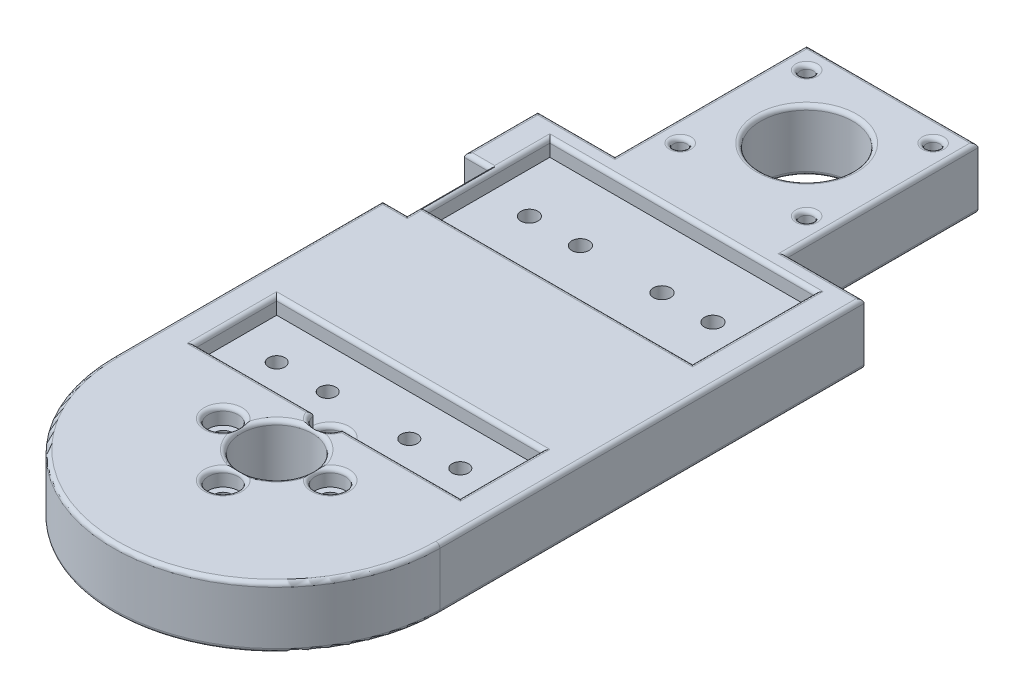
SolidWorks part; units mm, degrees
ref_plane "Ebene vorne" through (0, 0, 0) normal (0, 0, 1) x (1, 0, 0)
ref_plane "Ebene oben" through (0, 0, 0) normal (0, 1, 0) x (1, 0, 0)
ref_plane "Ebene rechts" through (0, 0, 0) normal (1, 0, 0) x (0, 0, -1)
sketch "Skizze1" plane through (0, 0, 0) normal (0, 1, 0) x (1, 0, 0)
  line L0 (-25.9794, -40) -> (25.9794, -40) construction
  line L2 (-40, 0) -> (-40, 104)
  line L4 (40, 0) -> (40, 104)
  line L5 (-40, 0) -> (40, 104) construction
  line L6 (-40, 104) -> (40, 0) construction
  line L9 (-40, 104) -> (-40, 78)
  line L12 (-40, 104) -> (40, 104)
  line L13 (-21.0848, 151) -> (20.9152, 109) construction
  line L21 (-21.0848, 104) -> (20.9152, 104)
  line L22 (-21.0848, 104) -> (-21.0848, 151)
  line L23 (-21.0848, 151) -> (20.9152, 151)
  line L24 (20.9152, 104) -> (20.9152, 151)
  line L25 (20.9152, 151) -> (-21.0848, 109) construction
  line L26 (0, 17.5) -> (0, 8.75) construction
  circle A0 centre (0, 0) radius 40
  circle A2 centre (-0.0848, 130) radius 11.3
  circle A3 centre (-15.5848, 145.5) radius 1.65
  circle A4 centre (15.4152, 145.5) radius 1.65
  circle A5 centre (15.4152, 114.5) radius 1.65
  circle A6 centre (-15.5848, 114.5) radius 1.65
  circle A7 centre (0, 0) radius 8.75
  circle A8 centre (0, 0) radius 17.5
  circle A17 centre (0, 13.125) radius 2.1
  circle A18 centre (13.125, 0) radius 2.1
  circle A19 centre (0, -13.125) radius 2.1
  circle A20 centre (-13.125, 0) radius 2.1
  point P7 (0, 52)
  point P11 (0, -40)
  point P31 (-0.0848, 130)
  point P35 (0, 0)
  point P36 (0, 13.125)
  point P44 (0, 0)
  point P52 (0, 0)
  dimension "D1" = 80
  dimension "D5" = 144
  dimension "D4" = 42
  dimension "D6" = 4
  dimension "D7" = 35
  dimension "D8" = 4
  dimension "D9" = 3.3
  dimension "D11" = 17.5
  dimension "D2" = 42
  dimension "D3" = 5
extrude "Aufsatz-Linear austragen1" add sketch "Skizze1" along normal blind 15 contours L12 L24 L23 L22 A6 A5 A4 A3 A2 | A0 L4 L12 L2 | A0 A8 | A8 A20 A19 A18 A17 A7
sketch "Skizze5" plane through (0, 15, 0) normal (0, 1, 0) x (1, 0, 0)
  line L0 (40, 0) -> (40, 104) construction
  line L1 (-25, 69.5) -> (40, 69.5)
  line L2 (-25, 69.5) -> (-25, 32.5)
  line L3 (-25, 32.5) -> (40, 32.5)
  line L4 (40, 69.5) -> (40, 32.5)
  line L5 (-25, 69.5) -> (40, 32.5) construction
  line L6 (-25, 32.5) -> (40, 69.5) construction
  line L7 (0, 0) -> (0, 22.5) construction
  line L8 (-25, 32.5) -> (40, 32.5)
  line L13 (20.9152, 104) -> (40, 104) construction
  line L14 (-32.5, 12.5) -> (32.5, 12.5)
  line L15 (-32.5, 12.5) -> (-32.5, 32.5)
  line L16 (-32.5, 32.5) -> (32.5, 32.5)
  line L17 (32.5, 12.5) -> (32.5, 32.5)
  line L18 (-32.5, 12.5) -> (32.5, 32.5) construction
  line L19 (-32.5, 32.5) -> (32.5, 12.5) construction
  point P4 (7.5, 51)
  point P13 (0, 22.5)
  dimension "D1" = 20
  dimension "D2" = 37
  dimension "D3" = 65
  dimension "D4" = 34.5
extrude "Schnitt-Linear austragen3" cut sketch "Skizze5" against normal blind 4 contours L14 L17 L3 L16 L15 region at (0, 15, -22.5)
sketch "Skizze6" plane through (0, 11, 0) normal (0, 1, 0) x (1, 0, 0)
  line L0 (-32.5, 22.5) -> (32.5, 22.5) construction
  line L1 (32.5, 12.5) -> (32.5, 32.5) construction
  line L3 (0, 22.5) -> (0, 3.2798) construction
  line L5 (32.5, 12.5) -> (32.5, 32.5) construction
  circle A0 centre (10, 22.5) radius 2
  circle A1 centre (-10, 22.5) radius 2
  circle A2 centre (22.5, 22.5) radius 2
  circle A3 centre (-22.5, 22.5) radius 2
  dimension "D2" = 4
  dimension "D3" = 4
  dimension "D1" = 10
  dimension "D4" = 12.5
extrude "Schnitt-Linear austragen4" cut sketch "Skizze6" against normal blind 11
sketch "Skizze14" plane through (0, 15, 0) normal (0, 1, 0) x (1, 0, 0)
  line L0 (-40, 104) -> (-40, 86) construction
  line L1 (-40, 0) -> (-40, 104) construction
  line L2 (-40, 104) -> (-21.0848, 104) construction
  line L4 (-40, 86) -> (-34, 86)
  line L5 (-40, 86) -> (-40, 66)
  line L6 (-40, 66) -> (-34, 66)
  line L7 (-34, 86) -> (-34, 66)
  line L8 (-40, 86) -> (-34, 66) construction
  line L9 (-40, 66) -> (-34, 86) construction
  point P9 (-37, 76)
  dimension "D1" = 20
  dimension "D2" = 18
  dimension "D3" = 6
extrude "Schnitt-Linear austragen11" cut sketch "Skizze14" against normal blind 15 contours L5 L4 L7 L6
sketch "Skizze15" plane through (-34, 0, 0) normal (-1, 0, 0) x (0, 0, 1)
  line L0 (-86, 0) -> (-86, 15) construction
  line L1 (-66, 0) -> (-66, 15) construction
  circle A1 centre (-80.5, 7.5) radius 2.25
  circle A2 centre (-71, 7.5) radius 2.25
  dimension "D1" = 4.5
  dimension "D2" = 4.5
  dimension "D3" = 9.5
  dimension "D4" = 5.5
  dimension "D5" = 5
extrude "Schnitt-Linear austragen12" cut sketch "Skizze15" against normal blind 6
sketch "Skizze19" plane through (0, 15, 0) normal (0, 1, 0) x (1, 0, 0)
  line L0 (0, 0) -> (-0.0848, 130) construction
  line L2 (-32.5551, 69.5) -> (32.4449, 69.5)
  line L3 (-32.5551, 69.5) -> (-32.5551, 99.5)
  line L4 (-32.5551, 99.5) -> (32.4449, 99.5)
  line L5 (32.4449, 69.5) -> (32.4449, 99.5)
  line L6 (-32.5551, 69.5) -> (32.4449, 99.5) construction
  line L7 (-32.5551, 99.5) -> (32.4449, 69.5) construction
  line L8 (20.9152, 104) -> (40, 104) construction
  point P4 (-0.0551, 84.5)
  dimension "D1" = 65
  dimension "D2" = 30
  dimension "D3" = 4.5
extrude "Schnitt-Linear austragen15" cut sketch "Skizze19" against normal blind 4
sketch "Skizze21" plane through (0, 11, 0) normal (0, 1, 0) x (1, 0, 0)
  line L1 (-0.0548, 84) -> (-0.0548, 95.2298) construction
  line L4 (32.4449, 69.5) -> (32.4449, 99.5) construction
  line L5 (-32.5551, 84.5) -> (32.4449, 84.5) construction
  line L6 (-32.5551, 99.5) -> (-32.5551, 69.5) construction
  circle A0 centre (22.4449, 84.5) radius 2.1
  circle A1 centre (9.9449, 84.5) radius 2.1
  circle A2 centre (-22.5545, 84.5) radius 2.1
  circle A3 centre (-10.0545, 84.5) radius 2.1
  point P13 (0, 0)
  point P18 (0, 0)
  point P19 (0, 0)
  dimension "D1" = 10
  dimension "D2" = 12.5
extrude "Schnitt-Linear austragen16" cut sketch "Skizze21" against normal blind 11
sketch "Skizze22" plane through (0, 0, 0) normal (0, -1, 0) x (1, 0, 0)
  line L0 (0, -84) -> (0, -79.7713) construction
  circle A0 centre (-22.5545, -84.5) radius 3.65
  circle A1 centre (-10.0545, -84.5) radius 3.65
  circle A2 centre (10.0545, -84.5) radius 3.65
  circle A3 centre (22.5545, -84.5) radius 3.65
  circle A4 centre (-22.5545, -84.5) radius 2.1 construction
  circle A5 centre (-10.0545, -84.5) radius 2.1 construction
  circle A6 centre (-22.5, -22.5) radius 3.65
  circle A7 centre (-10, -22.5) radius 3.65
  circle A8 centre (10, -22.5) radius 3.65
  circle A9 centre (22.5, -22.5) radius 3.65
  point P8 (-0.0486, -79.7713)
  dimension "D1" = 7.3
  dimension "D2" = 7.3
  dimension "D3" = 7.3
  dimension "D4" = 7.3
extrude "Schnitt-Linear austragen17" cut sketch "Skizze22" against normal blind 4
sketch "Skizze23" plane through (0, 0, 0) normal (0, -1, 0) x (1, 0, 0)
  circle A0 centre (-15.5848, -114.5) radius 3
  circle A1 centre (-0.0848, -130) radius 11.3
  circle A2 centre (15.4152, -114.5) radius 3
  circle A3 centre (15.4152, -145.5) radius 3
  circle A4 centre (-15.5848, -145.5) radius 3
  point P15 (-0.0848, -130)
  dimension "D1" = 4
extrude "Schnitt-Linear austragen18" cut sketch "Skizze23" against normal blind 3
sketch "Sketch5" plane through (0, 15, 0) normal (0, 1, 0) x (1, 0, 0)
  circle A12 centre (-13.125, 0) radius 3.65
  circle A13 centre (-13.125, 0) radius 2.1 construction
  circle A14 centre (0, 13.125) radius 3.65
  circle A15 centre (13.125, 0) radius 3.65
  circle A16 centre (0, -13.125) radius 3.65
  point P4 (0, 0)
  point P10 (0, 0)
  point P14 (0, 0)
  dimension "D1" = 7.3
  dimension "D2" = 4
extrude "Cut-Extrude3" cut sketch "Sketch5" against normal blind 4
sketch "Skizze24" plane through (0, 11, 0) normal (0, 1, 0) x (1, 0, 0)
  circle A0 centre (0, 13.125) radius 3.65
  dimension "D1" = 7.3
extrude "Schnitt-Linear austragen19" cut sketch "Skizze24" against normal blind 4
fillet "Verrundung1" radius 1 62 edges at (0, 15, 8.75) (-0.0848, 15, -118.7) (-15.5848, 15, -143.85) (15.4152, 15, -143.85) (15.4152, 15, -112.85) (-15.5848, 15, -112.85) (-34, 15, -76) (-37, 15, -86) (-40, 15, -95) (-30.5424, 15, -104) (-21.0848, 15, -127.5) (-0.0848, 15, -151) (20.9152, 15, -127.5) (30.4576, 15, -104) (40, 15, -52) (0, 15, 40) (-40, 15, -33) (-37, 15, -66) (-0.0551, 15, -99.5) (-32.5551, 15, -84.5) (-0.0551, 15, -69.5) (32.4449, 15, -84.5) (0, 15, 16.775) (13.125, 15, 3.65) (18.048, 15, -12.5) (32.5, 15, -22.5) (0, 15, -32.5) (-32.5, 15, -22.5) (-18.048, 15, -12.5) (0, 15, -9.475) (-13.125, 15, 3.65) (0, 0, 8.75) (0, 0, -11.025) (13.125, 0, 2.1) (0, 0, 15.225) (-13.125, 0, 2.1) (0, 0, 40) (40, 0, -52) (30.4576, 0, -104) (20.9152, 0, -127.5) (-0.0848, 0, -151) (-21.0848, 0, -127.5) (-30.5424, 0, -104) (-40, 0, -95) (-37, 0, -86) (-34, 0, -76) (-37, 0, -66) (-40, 0, -33) (-0.0848, 0, -118.7) (-22.5545, 0, -88.15) (22.5, 0, -18.85) (10, 0, -18.85) (-10, 0, -26.15) (-10.0545, 0, -88.15) (10.0545, 0, -80.85) (22.5545, 0, -80.85) (-22.5, 0, -26.15) (-15.5848, 0, -117.5) (15.4152, 0, -117.5) (15.4152, 0, -148.5) (-15.5848, 0, -148.5) (0, 11, -16.775)
